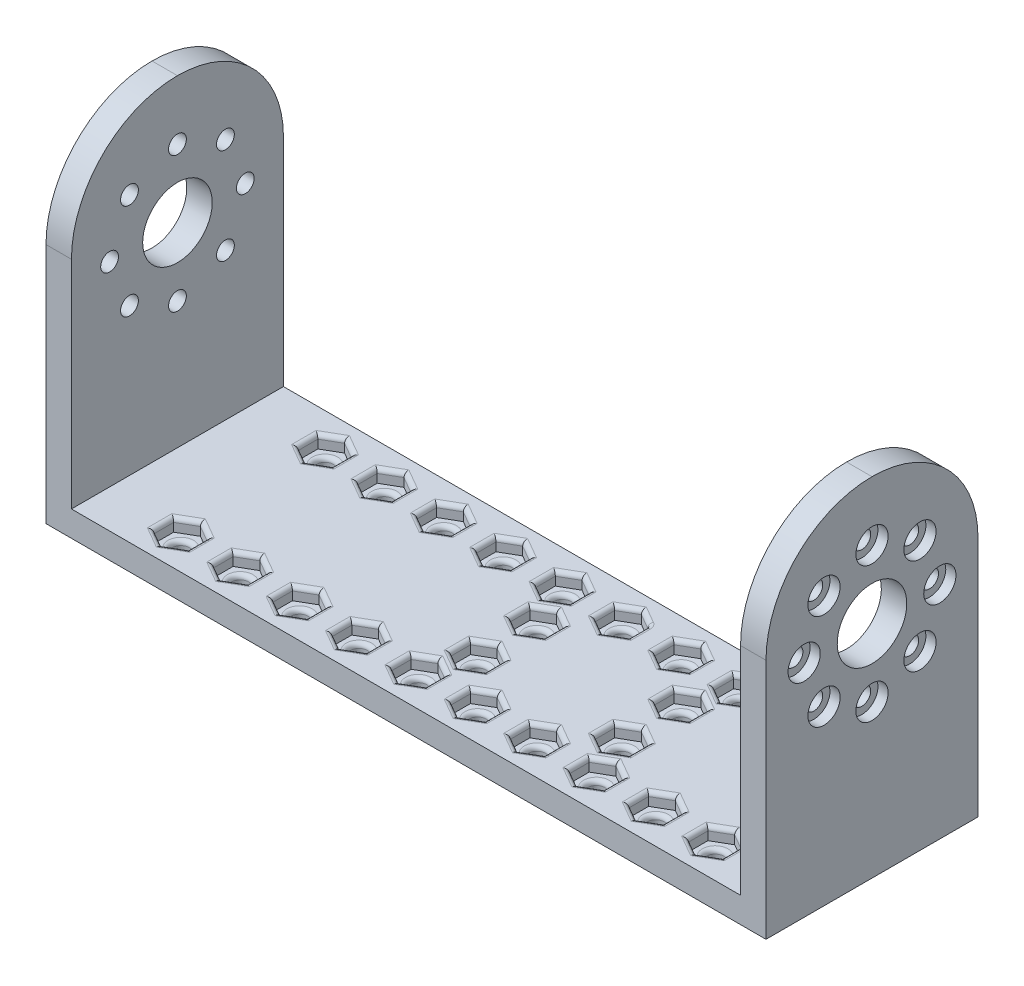
SolidWorks part; units mm, degrees
material "Polyamide"
ref_plane "Plan de face" through (0, 0, 0) normal (0, 0, 1) x (1, 0, 0)
ref_plane "Plan de dessus" through (0, 0, 0) normal (0, 1, 0) x (1, 0, 0)
ref_plane "Plan de droite" through (0, 0, 0) normal (1, 0, 0) x (0, 0, -1)
sketch "Sketch1" plane through (0, 0, 0) normal (0, 0, 1) x (1, 0, 0)
  line L0 (0, 0) -> (-42.45, 0)
  line L1 (-42.45, 0) -> (-42.45, 41)
  line L2 (-42.45, 41) -> (-39.45, 41)
  line L3 (-39.45, 41) -> (-39.45, 3)
  line L4 (-39.45, 3) -> (0, 3)
  line L5 (0, 3) -> (0, 0)
  dimension "D1" = 39.45
  dimension "D2" = 42.45
  dimension "D3" = 3
  dimension "D4" = 41
extrude "Boss-Extrude1" add sketch "Sketch1" along normal blind 25 contours L3 L4 L5 L0 L1 L2
sketch "Sketch2" plane through (-42.45, 0, 0) normal (-1, 0, 0) x (0, 0, 1)
  line L0 (0, 0) -> (0, 41) construction
  line L1 (25, 41) -> (0, 41) construction
  circle A0 centre (12.5, 26) radius 4.1
  dimension "D1" = 8.2
  dimension "D3" = 15
  dimension "D2" = 12.5
extrude "Cut-Extrude1" cut sketch "Sketch2" against normal up to surface (3 mm away) up to face at (-39.45, 22, 12.5)
sketch "Sketch3" plane through (-42.45, 0, 0) normal (-1, 0, 0) x (0, 0, 1)
  circle A0 centre (12.5, 34) radius 1.05
  circle A1 centre (12.5, 26) radius 4.1 construction
  dimension "D1" = 2.1
  dimension "D2" = 0
  dimension "D3" = 8
extrude "Cut-Extrude2" cut sketch "Sketch3" against normal up to surface (3 mm away) up to face at (-39.45, 30.1, 12.5)
sketch "Sketch4" plane through (-42.45, 0, 0) normal (-1, 0, 0) x (0, 0, 1)
  circle A0 centre (12.5, 34) radius 1.9
  dimension "D1" = 3.8
extrude "Cut-Extrude3" cut sketch "Sketch4" against normal blind 1.2 contours A0
pattern_circular "CirPattern1" count 8 over 360 about axis through (-42.45, 26, 12.5) along (-1, 0, 0) of "Cut-Extrude3", "Cut-Extrude2"
mirror "Mirror2" about plane through (0, 3, 25) normal (1, 0, 0) of "CirPattern1", "Boss-Extrude1", "Cut-Extrude1", "Cut-Extrude2", "Cut-Extrude3"
fillet "Congé1" radius 12.5 4 edges at (-40.95, 41, 0) (-40.95, 41, 25) (40.95, 41, 25) (40.95, 41, 0)
sketch "Esquisse1" plane through (0, 3, 0) normal (0, 1, 0) x (1, 0, 0)
  line L0 (7.95, -4) -> (7.95, -21) construction
  line L1 (-0.55, -12.5) -> (16.45, -12.5) construction
  line L2 (-0.55, -4) -> (16.45, -4) construction
  line L3 (16.45, -4) -> (16.45, -21) construction
  line L4 (16.45, -21) -> (-0.55, -21) construction
  line L5 (-0.55, -21) -> (-0.55, -4) construction
  line L6 (-0.55, -9) -> (16.45, -9) construction
  line L7 (4.45, -4) -> (4.45, -21) construction
  line L8 (-0.55, -16) -> (16.45, -16) construction
  line L9 (11.45, -4) -> (11.45, -21) construction
  line L10 (7.95, -1.5) -> (7.95, -23.5) construction
  line L11 (39.45, -25) -> (39.45, 0) construction
  line L12 (-39.45, 0) -> (39.45, 0) construction
  circle A0 centre (4.45, -4) radius 1
  circle A1 centre (-0.55, -9) radius 1
  circle A2 centre (-0.55, -16) radius 1
  circle A3 centre (4.45, -21) radius 1
  circle A4 centre (11.45, -21) radius 1
  circle A5 centre (16.45, -16) radius 1
  circle A6 centre (16.45, -9) radius 1
  circle A7 centre (11.45, -4) radius 1
  circle A8 centre (-2.55, -4) radius 1
  circle A9 centre (-2.55, -21) radius 1
  circle A10 centre (-9.55, -4) radius 1
  circle A11 centre (-9.55, -21) radius 1
  circle A12 centre (-16.55, -4) radius 1
  circle A13 centre (-16.55, -21) radius 1
  circle A14 centre (-23.55, -4) radius 1
  circle A15 centre (-23.55, -21) radius 1
  circle A16 centre (-30.55, -4) radius 1
  circle A17 centre (-30.55, -21) radius 1
  circle A18 centre (18.45, -4) radius 1
  circle A19 centre (18.45, -21) radius 1
  circle A20 centre (25.45, -4) radius 1
  circle A21 centre (25.45, -21) radius 1
  circle A22 centre (32.45, -4) radius 1
  circle A23 centre (32.45, -21) radius 1
  point P16 (7.95, -12.5)
  dimension "D1" = 23
  dimension "D2" = 7
  dimension "D3" = 5
  dimension "D4" = 5
  dimension "D5" = 7
  dimension "D6" = 2
  dimension "D7" = 4
  dimension "D8" = 6
  dimension "D9" = 4
extrude "Enlèv. mat.-Extru.1" cut sketch "Esquisse1" against normal blind 10
sketch "Sketch5" plane through (0, 3, 0) normal (0, 1, 0) x (1, 0, 0)
  line L1 (11.45, -6.3094) -> (13.45, -5.1547)
  line L2 (13.45, -5.1547) -> (13.45, -2.8453)
  line L3 (13.45, -2.8453) -> (11.45, -1.6906)
  line L4 (11.45, -1.6906) -> (9.45, -2.8453)
  line L5 (9.45, -2.8453) -> (9.45, -5.1547)
  line L6 (9.45, -5.1547) -> (11.45, -6.3094)
  line L7 (4.45, -6.3094) -> (6.45, -5.1547)
  line L8 (6.45, -5.1547) -> (6.45, -2.8453)
  line L9 (6.45, -2.8453) -> (4.45, -1.6906)
  line L10 (4.45, -1.6906) -> (2.45, -2.8453)
  line L11 (2.45, -2.8453) -> (2.45, -5.1547)
  line L12 (2.45, -5.1547) -> (4.45, -6.3094)
  line L13 (-0.55, -11.3094) -> (1.45, -10.1547)
  line L14 (1.45, -10.1547) -> (1.45, -7.8453)
  line L15 (1.45, -7.8453) -> (-0.55, -6.6906)
  line L16 (-0.55, -6.6906) -> (-2.55, -7.8453)
  line L17 (-2.55, -7.8453) -> (-2.55, -10.1547)
  line L18 (-2.55, -10.1547) -> (-0.55, -11.3094)
  line L19 (-0.55, -18.3094) -> (1.45, -17.1547)
  line L20 (1.45, -17.1547) -> (1.45, -14.8453)
  line L21 (1.45, -14.8453) -> (-0.55, -13.6906)
  line L22 (-0.55, -13.6906) -> (-2.55, -14.8453)
  line L23 (-2.55, -14.8453) -> (-2.55, -17.1547)
  line L24 (-2.55, -17.1547) -> (-0.55, -18.3094)
  line L25 (4.45, -23.3094) -> (6.45, -22.1547)
  line L26 (6.45, -22.1547) -> (6.45, -19.8453)
  line L27 (6.45, -19.8453) -> (4.45, -18.6906)
  line L28 (4.45, -18.6906) -> (2.45, -19.8453)
  line L29 (2.45, -19.8453) -> (2.45, -22.1547)
  line L30 (2.45, -22.1547) -> (4.45, -23.3094)
  line L31 (11.45, -23.3094) -> (13.45, -22.1547)
  line L32 (13.45, -22.1547) -> (13.45, -19.8453)
  line L33 (13.45, -19.8453) -> (11.45, -18.6906)
  line L34 (11.45, -18.6906) -> (9.45, -19.8453)
  line L35 (9.45, -19.8453) -> (9.45, -22.1547)
  line L36 (9.45, -22.1547) -> (11.45, -23.3094)
  line L37 (16.45, -18.3094) -> (18.45, -17.1547)
  line L38 (18.45, -17.1547) -> (18.45, -14.8453)
  line L39 (18.45, -14.8453) -> (16.45, -13.6906)
  line L40 (16.45, -13.6906) -> (14.45, -14.8453)
  line L41 (14.45, -14.8453) -> (14.45, -17.1547)
  line L42 (14.45, -17.1547) -> (16.45, -18.3094)
  line L43 (16.45, -11.3094) -> (18.45, -10.1547)
  line L44 (18.45, -10.1547) -> (18.45, -7.8453)
  line L45 (18.45, -7.8453) -> (16.45, -6.6906)
  line L46 (16.45, -6.6906) -> (14.45, -7.8453)
  line L47 (14.45, -7.8453) -> (14.45, -10.1547)
  line L48 (14.45, -10.1547) -> (16.45, -11.3094)
  line L49 (-2.55, -1.6906) -> (-4.55, -2.8453)
  line L50 (-4.55, -2.8453) -> (-4.55, -5.1547)
  line L51 (-4.55, -5.1547) -> (-2.55, -6.3094)
  line L52 (-2.55, -6.3094) -> (-0.55, -5.1547)
  line L53 (-0.55, -5.1547) -> (-0.55, -2.8453)
  line L54 (-0.55, -2.8453) -> (-2.55, -1.6906)
  line L55 (-9.55, -1.6906) -> (-11.55, -2.8453)
  line L56 (-11.55, -2.8453) -> (-11.55, -5.1547)
  line L57 (-11.55, -5.1547) -> (-9.55, -6.3094)
  line L58 (-9.55, -6.3094) -> (-7.55, -5.1547)
  line L59 (-7.55, -5.1547) -> (-7.55, -2.8453)
  line L60 (-7.55, -2.8453) -> (-9.55, -1.6906)
  line L61 (-16.55, -1.6906) -> (-18.55, -2.8453)
  line L62 (-18.55, -2.8453) -> (-18.55, -5.1547)
  line L63 (-18.55, -5.1547) -> (-16.55, -6.3094)
  line L64 (-16.55, -6.3094) -> (-14.55, -5.1547)
  line L65 (-14.55, -5.1547) -> (-14.55, -2.8453)
  line L66 (-14.55, -2.8453) -> (-16.55, -1.6906)
  line L67 (-23.55, -1.6906) -> (-25.55, -2.8453)
  line L68 (-25.55, -2.8453) -> (-25.55, -5.1547)
  line L69 (-25.55, -5.1547) -> (-23.55, -6.3094)
  line L70 (-23.55, -6.3094) -> (-21.55, -5.1547)
  line L71 (-21.55, -5.1547) -> (-21.55, -2.8453)
  line L72 (-21.55, -2.8453) -> (-23.55, -1.6906)
  line L73 (-30.55, -1.6906) -> (-32.55, -2.8453)
  line L74 (-32.55, -2.8453) -> (-32.55, -5.1547)
  line L75 (-32.55, -5.1547) -> (-30.55, -6.3094)
  line L76 (-30.55, -6.3094) -> (-28.55, -5.1547)
  line L77 (-28.55, -5.1547) -> (-28.55, -2.8453)
  line L78 (-28.55, -2.8453) -> (-30.55, -1.6906)
  line L79 (-30.55, -18.6906) -> (-32.55, -19.8453)
  line L80 (-32.55, -19.8453) -> (-32.55, -22.1547)
  line L81 (-32.55, -22.1547) -> (-30.55, -23.3094)
  line L82 (-30.55, -23.3094) -> (-28.55, -22.1547)
  line L83 (-28.55, -22.1547) -> (-28.55, -19.8453)
  line L84 (-28.55, -19.8453) -> (-30.55, -18.6906)
  line L85 (-23.55, -18.6906) -> (-25.55, -19.8453)
  line L86 (-25.55, -19.8453) -> (-25.55, -22.1547)
  line L87 (-25.55, -22.1547) -> (-23.55, -23.3094)
  line L88 (-23.55, -23.3094) -> (-21.55, -22.1547)
  line L89 (-21.55, -22.1547) -> (-21.55, -19.8453)
  line L90 (-21.55, -19.8453) -> (-23.55, -18.6906)
  line L91 (-16.55, -18.6906) -> (-18.55, -19.8453)
  line L92 (-18.55, -19.8453) -> (-18.55, -22.1547)
  line L93 (-18.55, -22.1547) -> (-16.55, -23.3094)
  line L94 (-16.55, -23.3094) -> (-14.55, -22.1547)
  line L95 (-14.55, -22.1547) -> (-14.55, -19.8453)
  line L96 (-14.55, -19.8453) -> (-16.55, -18.6906)
  line L97 (-9.55, -18.6906) -> (-11.55, -19.8453)
  line L98 (-11.55, -19.8453) -> (-11.55, -22.1547)
  line L99 (-11.55, -22.1547) -> (-9.55, -23.3094)
  line L100 (-9.55, -23.3094) -> (-7.55, -22.1547)
  line L101 (-7.55, -22.1547) -> (-7.55, -19.8453)
  line L102 (-7.55, -19.8453) -> (-9.55, -18.6906)
  line L103 (-2.55, -18.6906) -> (-4.55, -19.8453)
  line L104 (-4.55, -19.8453) -> (-4.55, -22.1547)
  line L105 (-4.55, -22.1547) -> (-2.55, -23.3094)
  line L106 (-2.55, -23.3094) -> (-0.55, -22.1547)
  line L107 (-0.55, -22.1547) -> (-0.55, -19.8453)
  line L108 (-0.55, -19.8453) -> (-2.55, -18.6906)
  line L109 (18.45, -18.6906) -> (16.45, -19.8453)
  line L110 (16.45, -19.8453) -> (16.45, -22.1547)
  line L111 (16.45, -22.1547) -> (18.45, -23.3094)
  line L112 (18.45, -23.3094) -> (20.45, -22.1547)
  line L113 (20.45, -22.1547) -> (20.45, -19.8453)
  line L114 (20.45, -19.8453) -> (18.45, -18.6906)
  line L115 (25.45, -18.6906) -> (23.45, -19.8453)
  line L116 (23.45, -19.8453) -> (23.45, -22.1547)
  line L117 (23.45, -22.1547) -> (25.45, -23.3094)
  line L118 (25.45, -23.3094) -> (27.45, -22.1547)
  line L119 (27.45, -22.1547) -> (27.45, -19.8453)
  line L120 (27.45, -19.8453) -> (25.45, -18.6906)
  line L121 (32.45, -18.6906) -> (30.45, -19.8453)
  line L122 (30.45, -19.8453) -> (30.45, -22.1547)
  line L123 (30.45, -22.1547) -> (32.45, -23.3094)
  line L124 (32.45, -23.3094) -> (34.45, -22.1547)
  line L125 (34.45, -22.1547) -> (34.45, -19.8453)
  line L126 (34.45, -19.8453) -> (32.45, -18.6906)
  line L127 (18.45, -1.6906) -> (16.45, -2.8453)
  line L128 (16.45, -2.8453) -> (16.45, -5.1547)
  line L129 (16.45, -5.1547) -> (18.45, -6.3094)
  line L130 (18.45, -6.3094) -> (20.45, -5.1547)
  line L131 (20.45, -5.1547) -> (20.45, -2.8453)
  line L132 (20.45, -2.8453) -> (18.45, -1.6906)
  line L133 (25.45, -1.6906) -> (23.45, -2.8453)
  line L134 (23.45, -2.8453) -> (23.45, -5.1547)
  line L135 (23.45, -5.1547) -> (25.45, -6.3094)
  line L136 (25.45, -6.3094) -> (27.45, -5.1547)
  line L137 (27.45, -5.1547) -> (27.45, -2.8453)
  line L138 (27.45, -2.8453) -> (25.45, -1.6906)
  line L139 (32.45, -1.6906) -> (30.45, -2.8453)
  line L140 (30.45, -2.8453) -> (30.45, -5.1547)
  line L141 (30.45, -5.1547) -> (32.45, -6.3094)
  line L142 (32.45, -6.3094) -> (34.45, -5.1547)
  line L143 (34.45, -5.1547) -> (34.45, -2.8453)
  line L144 (34.45, -2.8453) -> (32.45, -1.6906)
  circle A0 centre (11.45, -4) radius 2 construction
  circle A1 centre (4.45, -4) radius 2 construction
  circle A2 centre (-0.55, -9) radius 2 construction
  circle A3 centre (-0.55, -16) radius 2 construction
  circle A4 centre (4.45, -21) radius 2 construction
  circle A5 centre (11.45, -21) radius 2 construction
  circle A6 centre (16.45, -16) radius 2 construction
  circle A7 centre (16.45, -9) radius 2 construction
  circle A8 centre (-2.55, -4) radius 2 construction
  circle A9 centre (-9.55, -4) radius 2 construction
  circle A10 centre (-16.55, -4) radius 2 construction
  circle A11 centre (-23.55, -4) radius 2 construction
  circle A12 centre (-30.55, -4) radius 2 construction
  circle A13 centre (-30.55, -21) radius 2 construction
  circle A14 centre (-23.55, -21) radius 2 construction
  circle A15 centre (-16.55, -21) radius 2 construction
  circle A16 centre (-9.55, -21) radius 2 construction
  circle A17 centre (-2.55, -21) radius 2 construction
  circle A18 centre (18.45, -21) radius 2 construction
  circle A19 centre (25.45, -21) radius 2 construction
  circle A20 centre (32.45, -21) radius 2 construction
  circle A21 centre (18.45, -4) radius 2 construction
  circle A22 centre (25.45, -4) radius 2 construction
  circle A23 centre (32.45, -4) radius 2 construction
  dimension "D1" = 4
  dimension "D2" = 4
  dimension "D3" = 4
  dimension "D4" = 4
  dimension "D5" = 4
  dimension "D6" = 4
  dimension "D7" = 4
  dimension "D8" = 4
  dimension "D9" = 4
  dimension "D10" = 4
  dimension "D11" = 4
  dimension "D12" = 4
  dimension "D13" = 4
  dimension "D14" = 4
  dimension "D15" = 4
  dimension "D16" = 4
  dimension "D17" = 4
  dimension "D18" = 4
  dimension "D19" = 4
  dimension "D20" = 4
  dimension "D21" = 4
  dimension "D22" = 4
  dimension "D23" = 4
  dimension "D24" = 4
extrude "Cut-Extrude4" cut sketch "Sketch5" against normal blind 1.5
fillet "Fillet1" radius 0.5 169 edges at (16.45, 1.5, 17) (4.45, 1.5, 5) (11.45, 1.5, 5) (16.45, 1.5, 10) (11.45, 1.5, 22) (-0.55, 1.5, 10) (-0.55, 1.5, 17) (4.45, 1.5, 22) (6.45, 3, 4) (13.45, 3, 4) (12.45, 3, 2.2679) (10.45, 3, 2.2679) (9.45, 3, 4) (10.45, 3, 5.7321) (12.45, 3, 5.7321) (17.45, 3, 7.2679) (15.45, 3, 7.2679) (14.45, 3, 9) (15.45, 3, 10.7321) (17.45, 3, 10.7321) (18.45, 3, 9) (17.45, 3, 14.2679) (18.45, 3, 16) (17.45, 3, 17.7321) (15.45, 3, 17.7321) (14.45, 3, 16) (15.45, 3, 14.2679) (3.45, 3, 5.7321) (5.45, 3, 5.7321) (6.45, 2.25, 2.8453) (5.45, 3, 2.2679) (3.45, 3, 2.2679) (2.45, 3, 4) (-1.55, 3, 10.7321) (-2.55, 3, 9) (-1.55, 3, 7.2679) (0.45, 3, 7.2679) (1.45, 3, 9) (0.45, 3, 10.7321) (-1.55, 3, 17.7321) (-2.55, 3, 16) (-1.55, 3, 14.2679) (0.45, 3, 14.2679) (1.45, 3, 16) (0.45, 3, 17.7321) (5.45, 3, 19.2679) (3.45, 3, 19.2679) (2.45, 3, 21) (3.45, 3, 22.7321) (5.45, 3, 22.7321) (6.45, 3, 21) (9.45, 3, 21) (10.45, 3, 22.7321) (12.45, 3, 22.7321) (13.45, 3, 21) (12.45, 3, 19.2679) (10.45, 3, 19.2679) (17.45, 3, 2.2679) (16.45, 3, 4) (17.45, 3, 5.7321) (19.45, 3, 5.7321) (19.45, 3, 2.2679) (20.45, 3, 4) (31.45, 3, 19.2679) (30.45, 3, 21) (31.45, 3, 22.7321) (34.45, 3, 21) (33.45, 3, 19.2679) (33.45, 3, 22.7321) (24.45, 3, 19.2679) (23.45, 3, 21) (24.45, 3, 22.7321) (27.45, 3, 21) (26.45, 3, 19.2679) (26.45, 3, 22.7321) (17.45, 3, 19.2679) (16.45, 3, 21) (17.45, 3, 22.7321) (19.45, 3, 22.7321) (19.45, 3, 19.2679) (20.45, 3, 21) (-3.55, 3, 19.2679) (-4.55, 3, 21) (-3.55, 3, 22.7321) (-0.55, 3, 21) (-1.55, 3, 19.2679) (-1.55, 3, 22.7321) (-10.55, 3, 19.2679) (-7.55, 3, 21) (-8.55, 3, 19.2679) (-11.55, 3, 21) (-10.55, 3, 22.7321) (-8.55, 3, 22.7321) (-17.55, 3, 22.7321) (-15.55, 3, 22.7321) (-14.55, 3, 21) (-15.55, 3, 19.2679) (-17.55, 3, 19.2679) (-18.55, 3, 21) (-25.55, 3, 21) (-24.55, 3, 22.7321) (-22.55, 3, 22.7321) (-21.55, 3, 21) (-22.55, 3, 19.2679) (-24.55, 3, 19.2679) (-29.55, 3, 19.2679) (-31.55, 3, 19.2679) (-32.55, 3, 21) (-31.55, 3, 22.7321) (-29.55, 3, 22.7321) (-28.55, 3, 21) (-29.55, 3, 2.2679) (-31.55, 3, 2.2679) (-32.55, 3, 4) (-31.55, 3, 5.7321) (-29.55, 3, 5.7321) (-28.55, 3, 4) (-22.55, 3, 2.2679) (-24.55, 3, 2.2679) (-25.55, 3, 4) (-24.55, 3, 5.7321) (-22.55, 3, 5.7321) (-21.55, 3, 4) (-15.55, 3, 2.2679) (-17.55, 3, 2.2679) (-18.55, 3, 4) (-17.55, 3, 5.7321) (-15.55, 3, 5.7321) (-14.55, 3, 4) (-8.55, 3, 2.2679) (-10.55, 3, 2.2679) (-11.55, 3, 4) (-10.55, 3, 5.7321) (-8.55, 3, 5.7321) (-7.55, 3, 4) (-1.55, 3, 2.2679) (-3.55, 3, 2.2679) (-4.55, 3, 4) (-3.55, 3, 5.7321) (-1.55, 3, 5.7321) (-0.55, 3, 4) (26.45, 3, 2.2679) (24.45, 3, 2.2679) (23.45, 3, 4) (24.45, 3, 5.7321) (26.45, 3, 5.7321) (27.45, 3, 4) (33.45, 3, 5.7321) (31.45, 3, 5.7321) (30.45, 3, 4) (31.45, 3, 2.2679) (33.45, 3, 2.2679) (34.45, 3, 4) (32.45, 1.5, 5) (25.45, 1.5, 5) (18.45, 1.5, 5) (32.45, 1.5, 22) (25.45, 1.5, 22) (18.45, 1.5, 22) (-2.55, 1.5, 22) (-9.55, 1.5, 22) (-16.55, 1.5, 22) (-23.55, 1.5, 22) (-30.55, 1.5, 22) (-30.55, 1.5, 5) (-23.55, 1.5, 5) (-16.55, 1.5, 5) (-9.55, 1.5, 5) (-2.55, 1.5, 5)
